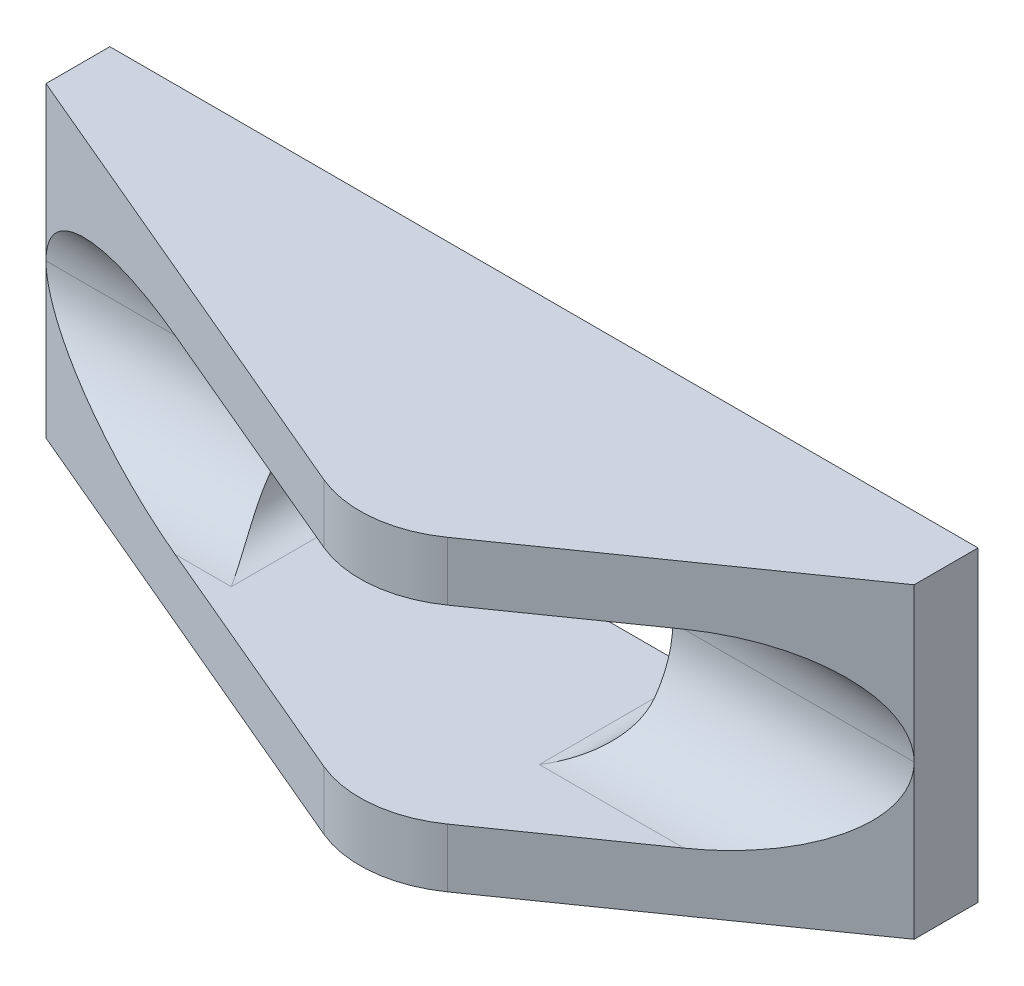
SolidWorks part; units mm, degrees
ref_plane "Front Plane" through (0, 0, 0) normal (0, 0, 1) x (1, 0, 0)
ref_plane "Top Plane" through (0, 0, 0) normal (0, 1, 0) x (1, 0, 0)
ref_plane "Right Plane" through (0, 0, 0) normal (1, 0, 0) x (0, 0, -1)
sketch "Sketch1" plane through (0, 0, 0) normal (0, 1, 0) x (1, 0, 0)
  line L0 (-26.3906, 12.2204) -> (30.5943, 12.2204)
  line L5 (-26.3906, 12.2204) -> (5.2363, -1.1741)
  line L6 (12.5798, -0.3985) -> (30.5943, 12.2204)
  line L7 (9.1229, -2.8201) -> (16.7104, -19.0915) construction
  line L8 (9.1229, -2.8201) -> (32.9999, -2.8201) construction
  line L10 (-26.3906, 12.2204) -> (-26.3906, 16.4114)
  line L11 (-26.3906, 16.4114) -> (30.5943, 16.4114)
  line L12 (30.5943, 12.2204) -> (30.5943, 16.4114)
  line L13 (9.1229, -2.8201) -> (2.1094, 12.2204) construction
  line L14 (2.1018, 16.4114) -> (2.1018, -38.2459) construction
  arc A0 (5.2363, -1.1741) -> (12.5798, -0.3985) centre (8.208, 5.8426) ccw
  dimension "D5" = 7.62
  dimension "D1" = 4.191
  dimension "D2" = 56.9849
  dimension "D3" = 65
  dimension "D4" = 180
extrude "Boss-Extrude2" add sketch "Sketch1" along normal mid plane 20.1549 contours L0 L12 L11 L10 | L5 A0 L6 L0 region at (2.1018, 0, -14.3159) region at (4.4121, 0, -7.2671)
extrude "Cut-Extrude2" cut sketch "Sketch1<16>" against normal mid plane 12.446 contours L5 A0 L6 L0 region at (4.4121, 0, -7.2671)
sketch "Sketch1<16>" plane through (0, 0, 0) normal (0, 1, 0) x (1, 0, 0) same geometry as "Sketch1"
fillet "Fillet8" radius 6.223 2 edges at (2.1018, -6.223, -12.2204) (2.1018, 6.223, -12.2204)
sketch "Sketch3" plane through (0, 0, -16.4114) normal (0, 0, -1) x (-1, 0, 0)
  line L0 (26.3906, 0) -> (-30.5943, 0) construction
  line L1 (-12.211, -6.223) -> (8.0074, -6.223)
  line L2 (-14.751, -3.683) -> (-14.751, 3.683)
  line L3 (-12.211, 6.223) -> (8.0074, 6.223)
  line L4 (10.5474, -3.683) -> (10.5474, 3.683)
  line L5 (-14.751, -6.223) -> (10.5474, 6.223) construction
  line L6 (-14.751, 6.223) -> (10.5474, -6.223) construction
  arc A0 (-12.211, -6.223) -> (-14.751, -3.683) centre (-12.211, -3.683) cw
  arc A1 (8.0074, -6.223) -> (10.5474, -3.683) centre (8.0074, -3.683) ccw
  arc A2 (8.0074, 6.223) -> (10.5474, 3.683) centre (8.0074, 3.683) cw
  arc A3 (-14.751, 3.683) -> (-12.211, 6.223) centre (-12.211, 3.683) cw
  point P0 (-2.1018, 0)
  dimension "D3" = 2.54
  dimension "D1" = 25.2984
  dimension "D2" = 12.446
extrude "Cut-Extrude5" cut sketch "Sketch3" against normal through all
sketch "Sketch2" plane through (0, 0, 20.4734) normal (0, 0, -1) x (-1, 0, 0)
  line L0 (16.0858, 0) -> (-40.8991, 0) construction
  line L1 (-25.0558, -6.223) -> (0.2426, -6.223)
  line L2 (-25.0558, -6.223) -> (-25.0558, 6.223)
  line L3 (-25.0558, 6.223) -> (0.2426, 6.223)
  line L4 (0.2426, -6.223) -> (0.2426, 6.223)
  line L5 (-25.0558, -6.223) -> (0.2426, 6.223) construction
  line L6 (-25.0558, 6.223) -> (0.2426, -6.223) construction
  point P0 (-12.4066, 0)
  dimension "D1" = 25.2984
  dimension "D2" = 12.446
